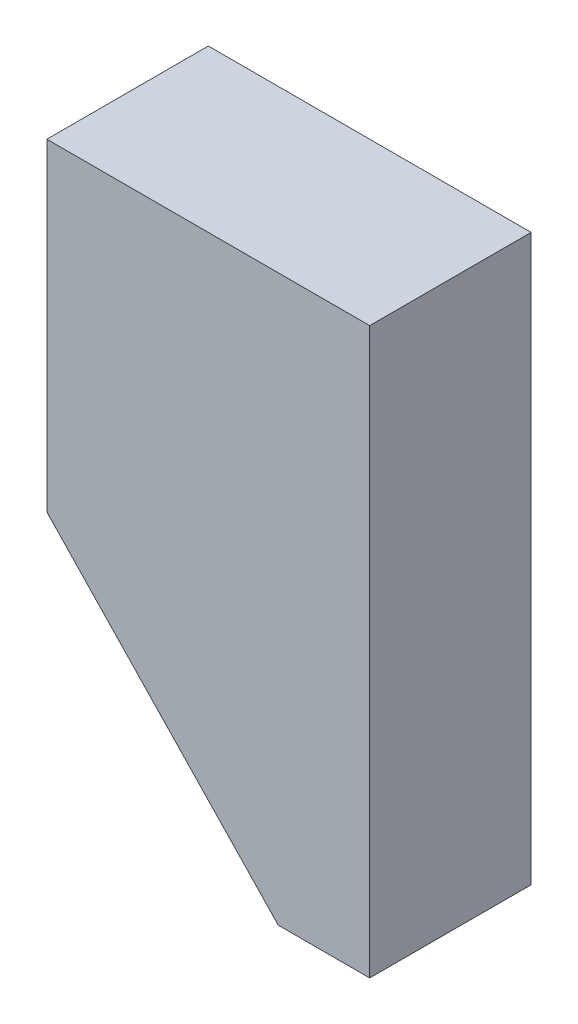
SolidWorks part; units mm, degrees
material "Pine"
ref_plane "Front Plane" through (0, 0, 0) normal (0, 0, 1) x (1, 0, 0)
ref_plane "Top Plane" through (0, 0, 0) normal (0, 1, 0) x (1, 0, 0)
ref_plane "Right Plane" through (0, 0, 0) normal (1, 0, 0) x (0, 0, -1)
sketch "Sketch1" plane through (0, 0, 0) normal (0, 0, 1) x (1, 0, 0)
  line L0 (56.8019, -126.3316) -> (35.2119, -126.3316) construction
  line L1 (-19.3981, 7.0184) -> (56.8019, 7.0184)
  line L2 (-19.3981, 7.0184) -> (-19.3981, -69.1816)
  line L3 (35.2119, -126.3316) -> (56.8019, -126.3316)
  line L4 (56.8019, 7.0184) -> (56.8019, -126.3316)
  line L5 (-19.3981, 7.0184) -> (-19.3981, -69.1816) construction
  line L6 (35.2119, -126.3316) -> (-19.3981, -69.1816)
  dimension "D1" = 76.2
  dimension "D2" = 133.35
  dimension "D3" = 21.59
  dimension "D4" = 76.2
extrude "Boss-Extrude1" add sketch "Sketch1" along normal blind 38.1
